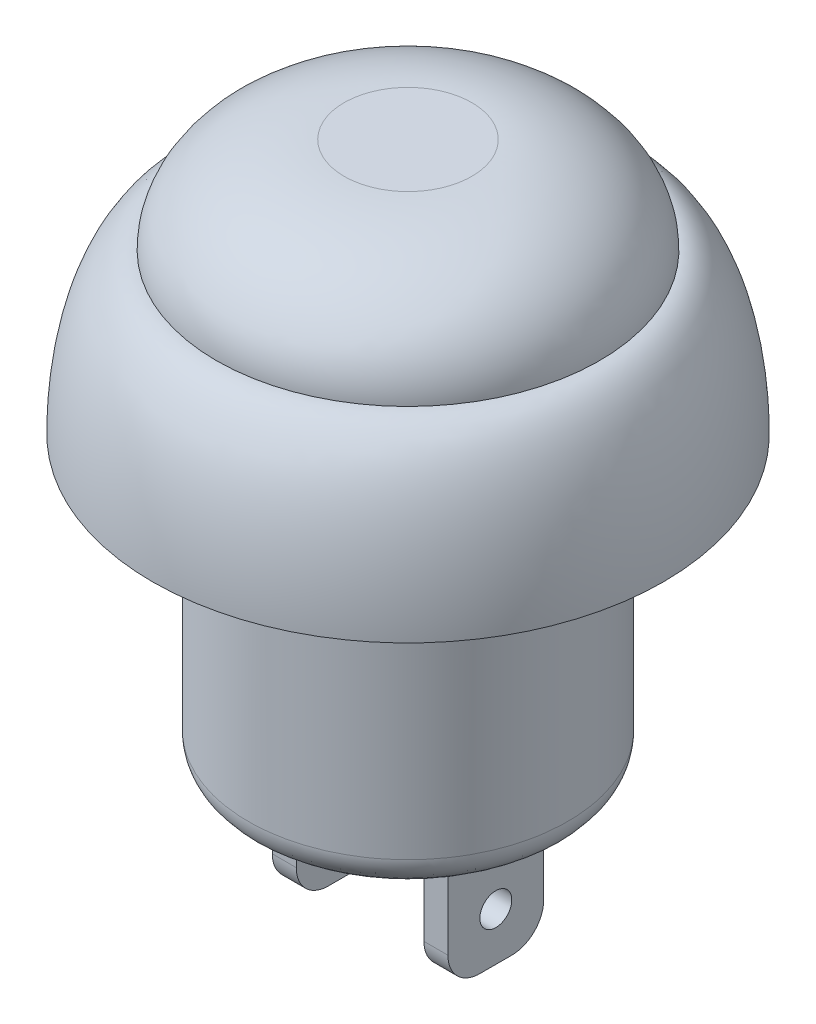
SolidWorks part; units mm, degrees
ref_plane "Front Plane" through (0, 0, 0) normal (0, 0, 1) x (1, 0, 0)
ref_plane "Top Plane" through (0, 0, 0) normal (0, 1, 0) x (1, 0, 0)
ref_plane "Right Plane" through (0, 0, 0) normal (1, 0, 0) x (0, 0, -1)
sketch "Sketch1" plane through (0, 0, 0) normal (0, 1, 0) x (1, 0, 0)
  circle A0 centre (0, 0) radius 8
  dimension "D1" = 16
extrude "Boss-Extrude1" add sketch "Sketch1" along normal blind 5
fillet "Fillet2" radius 5 1 edges at (0, 5, 8) second distance 2 first distance on face at (0, 5, 8)
sketch "Sketch2" plane through (0, 5, 0) normal (0, 1, 0) x (1, 0, 0)
  circle A0 centre (0, 0) radius 6
  dimension "D1" = 12
extrude "Boss-Extrude2" add sketch "Sketch2" along normal blind 3
fillet "Fillet3" radius 3 1 edges at (0, 8, 6) second distance 4 first distance on face at (0, 8, 6)
sketch "Sketch3" plane through (0, 0, 0) normal (0, -1, 0) x (1, 0, 0)
  circle A0 centre (0, 0) radius 6
  dimension "D1" = 12
extrude "Boss-Extrude3" add sketch "Sketch3" along normal blind 1 separate body
sketch "Sketch4" plane through (0, -1, 0) normal (0, -1, 0) x (1, 0, 0)
  circle A0 centre (0, 0) radius 5
  dimension "D1" = 10
extrude "Boss-Extrude4" add sketch "Sketch4" along normal blind 8 separate body
fillet "Fillet4" radius 1 1 edges at (0, -9, -5) first distance on face at (0, -9, -5)
sketch "Sketch5" plane through (0, -9, 0) normal (0, -1, 0) x (1, 0, 0)
  line L1 (-2.75, -1.5) -> (-2, -1.5)
  line L2 (-2.75, -1.5) -> (-2.75, 1.5)
  line L3 (-2.75, 1.5) -> (-2, 1.5)
  line L4 (-2, -1.5) -> (-2, 1.5)
  line L5 (-2.75, -1.5) -> (-2, 1.5) construction
  line L6 (-2.75, 1.5) -> (-2, -1.5) construction
  line L7 (2, -1.5) -> (2.75, -1.5)
  line L8 (2, -1.5) -> (2, 1.5)
  line L9 (2, 1.5) -> (2.75, 1.5)
  line L10 (2.75, -1.5) -> (2.75, 1.5)
  line L11 (2, -1.5) -> (2.75, 1.5) construction
  line L12 (2, 1.5) -> (2.75, -1.5) construction
  point P0 (-2.375, 0)
  point P5 (2.375, 0)
  dimension "D1" = 0.75
  dimension "D2" = 0.75
  dimension "D3" = 2
  dimension "D4" = 2
  dimension "D5" = 3
  dimension "D6" = 3
extrude "Boss-Extrude5" add sketch "Sketch5" along normal blind 4 separate body
fillet "Fillet5" radius 1 2 edges at (-2.375, -13, -1.5) (-2.375, -13, 1.5) first distance on face at (-2.375, -11, -1.5) first distance on face at (-2.375, -11, 1.5)
fillet "Fillet6" radius 1 2 edges at (2.375, -13, -1.5) (2.375, -13, 1.5) first distance on face at (2.375, -11, -1.5) first distance on face at (2.375, -11, 1.5)
sketch "Sketch6" plane through (-2.75, 0, 0) normal (-1, 0, 0) x (0, 0, 1)
  line L0 (0.5, -13) -> (-0.5, -13) construction
  circle A0 centre (0, -11.5) radius 0.5
  dimension "D1" = 1.5
extrude "Cut-Extrude1" cut sketch "Sketch6" against normal up to surface (5.5 mm away) up to face at (2.75, -11.4009, 0.026)
